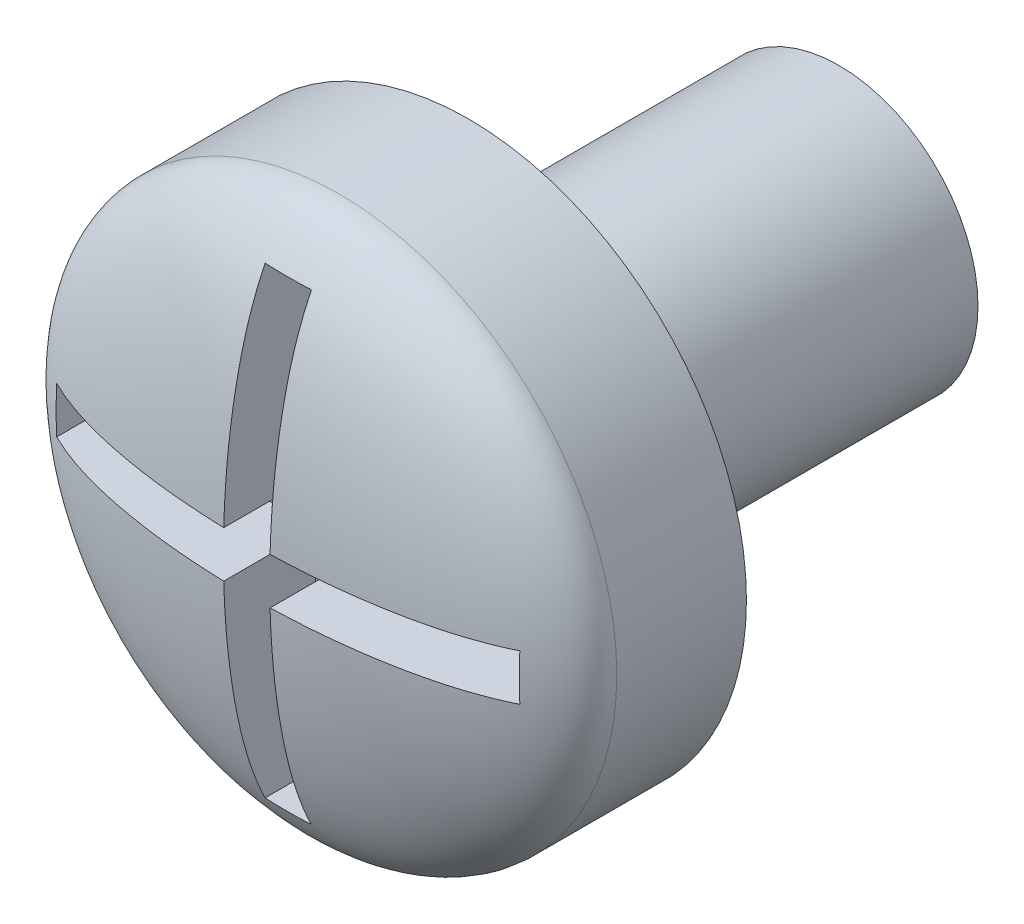
SolidWorks part; units mm, degrees
ref_plane "Front Plane" through (0, 0, 0) normal (0, 0, 1) x (1, 0, 0)
ref_plane "Top Plane" through (0, 0, 0) normal (0, 1, 0) x (1, 0, 0)
ref_plane "Right Plane" through (0, 0, 0) normal (1, 0, 0) x (0, 0, -1)
sketch "Sketch1" plane through (0, 0, 0) normal (0, 0, 1) x (1, 0, 0)
  circle A0 centre (0, 0) radius 3
  dimension "D1" = 6
extrude "Boss-Extrude3" add sketch "Sketch1" against normal blind 1.4 from offset 1 offset against normal yes
dome "Dome1" faces to dome 1 distance 1 reverse direction no elliptical dome yes face at (3, 0, -1) parameters "D1"=1
sketch "Sketch4" plane through (0, 0, -2.4) normal (0, 0, -1) x (-1, 0, 0)
  circle A0 centre (0, 0) radius 1.5
  dimension "D1" = 3
extrude "Boss-Extrude4" add sketch "Sketch4" along normal blind 4
sketch "Sketch5" plane through (0, 0, 0) normal (0, 0, 1) x (1, 0, 0)
  line L0 (0, 2.5) -> (0, -2.5) construction
  line L1 (-2.5, 0) -> (2.5, 0) construction
  line L2 (0, 2.5) -> (0, 3) construction
  line L3 (-0.25, 2.5) -> (0.25, 2.5)
  line L4 (-0.25, 2.5) -> (-0.25, -2.5)
  line L5 (-0.25, -2.5) -> (0.25, -2.5)
  line L6 (0.25, 2.5) -> (0.25, -2.5)
  line L7 (-2.5, 0.25) -> (2.5, 0.25)
  line L8 (-2.5, 0.25) -> (-2.5, -0.25)
  line L9 (-2.5, -0.25) -> (2.5, -0.25)
  line L10 (2.5, 0.25) -> (2.5, -0.25)
  circle A0 centre (0, 0) radius 3 construction
  point P6 (0, 0)
  dimension "D1" = 0.5
  dimension "D2" = 0.5
extrude "Cut-Extrude1" cut sketch "Sketch5" against normal blind 1 contours L8 L9 L4 L7 | L4 L9 L6 L7 | L4 L7 L6 L3 | L10 L7 L6 L9 | L9 L4 L5 L6 region at (0, 1.375, 0) region at (0, 0, 0) region at (-1.375, 0, 0) region at (1.375, 0, 0) region at (0, -1.375, 0)
